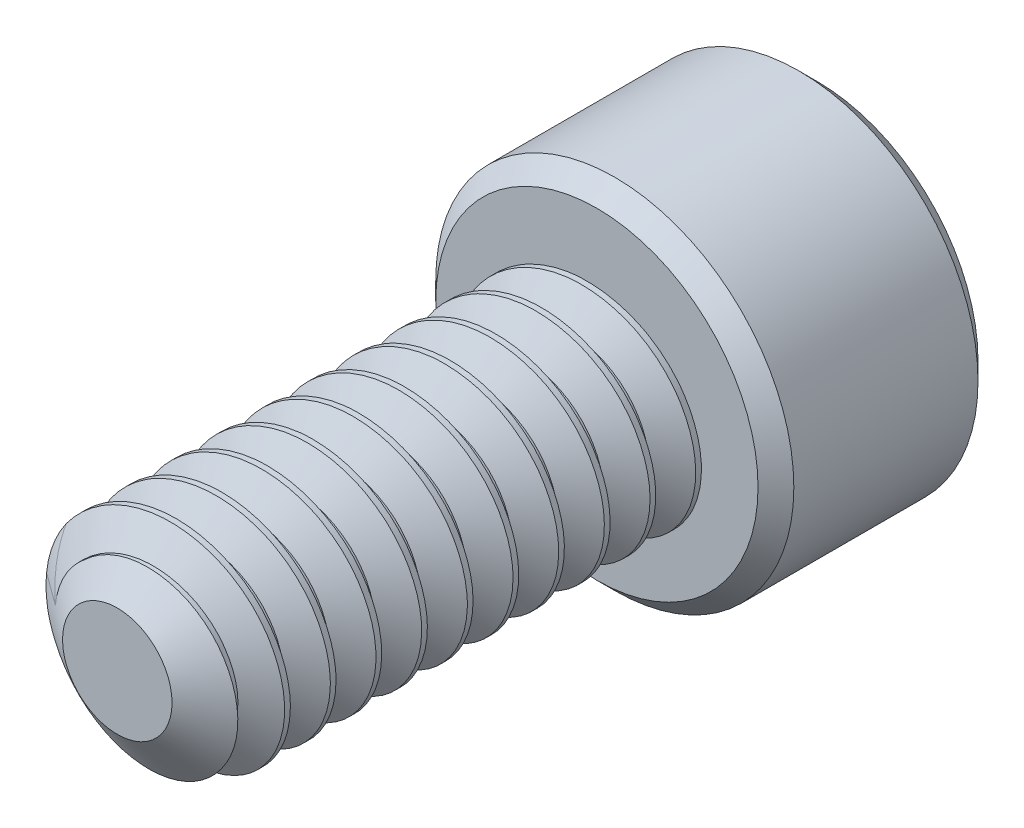
SolidWorks part; units mm, degrees
other "DetailItem1"
material "7075-T6 (SN)"
ref_plane "Front Plane" through (0, 0, 0) normal (0, 0, 1) x (1, 0, 0)
ref_plane "Top Plane" through (0, 0, 0) normal (0, 1, 0) x (1, 0, 0)
ref_plane "Right Plane" through (0, 0, 0) normal (1, 0, 0) x (0, 0, -1)
sketch "Sketch1" plane through (0, 0, 0) normal (0, 0, 1) x (1, 0, 0)
  circle A0 centre (0, 0) radius 1.0922
  dimension "OD" = 2.1844
extrude "Extrude1" add sketch "Sketch1" against normal blind 4.7625
sketch "Sketch2" plane through (0, 0, 0) normal (0, 0, 1) x (1, 0, 0)
  circle A0 centre (0, 0) radius 1.0922 construction
  circle A1 centre (0, 0) radius 1.0922
curve "Helix/Spiral1" pitch 0.4536 height 5.2161 radius 1.0922 centre (0, 0, 0) axis (0, 0, -1) start towards (0, 1, 0) parameters "pitch"=0.4536
sketch "Sketch3" plane through (0, 0, 0) normal (1, 0, 0) x (0, 0, -1)
  line L0 (-0.3969, 1.0922) -> (-0.2268, 0.7976)
  line L1 (-0.2268, 0.7976) -> (-0.1701, 0.7976)
  line L2 (-0.1701, 0.7976) -> (0, 1.0922)
  line L3 (-0.3969, 1.0922) -> (0, 1.0922)
  line L4 (-0.1984, 1.0922) -> (-0.1984, 0.7976) construction
  line L5 (-0.3118, 0.9449) -> (-0.085, 0.9449) construction
  line L6 (0, 1.0922) -> (0, -1.0922) construction
  dimension "D1" = 0.0567
  dimension "D2" = 0.2268
  dimension "D3" = 60
sweep "Cut-Sweep1" cut profiles "Sketch3" path "Helix/Spiral1" align with end faces yes
sketch "Sketch4" plane through (0, 0, 0) normal (1, 0, 0) x (0, 0, -1)
  line L0 (0.3841, 1.0922) -> (0, 0.5436)
  line L1 (0, 0.5436) -> (0, 1.0922)
  line L2 (0.3841, 1.0922) -> (0, 1.0922)
  line L3 (-0.3969, 1.0922) -> (0, 1.0922) construction
  line L4 (0, 0) -> (7.0209, 0) construction
  dimension "D1" = 55
  dimension "D2" = 0.254
revolve "Cut-Revolve1" cut sketch "Sketch4" angle 360 about L4
sketch "Sketch6" plane through (0, 0, -4.7625) normal (0, 0, -1) x (-1, 0, 0)
  circle A0 centre (0, 0) radius 1.778
  dimension "head dia" = 3.556
extrude "Extrude2" add sketch "Sketch6" along normal blind 2.1844
sketch "Sketch7" plane through (0, 0, -6.9469) normal (0, 0, -1) x (-1, 0, 0)
  line L1 (0, 1.1457) -> (-0.9922, 0.5728)
  line L2 (-0.9922, 0.5728) -> (-0.9922, -0.5728)
  line L3 (-0.9922, -0.5728) -> (0, -1.1457)
  line L4 (0, -1.1457) -> (0.9922, -0.5728)
  line L5 (0.9922, -0.5728) -> (0.9922, 0.5728)
  line L6 (0.9922, 0.5728) -> (0, 1.1457)
  circle A0 centre (0, 0) radius 0.9922 construction
  dimension "hex dia" = 1.9844
extrude "Cut-Extrude1" cut sketch "Sketch7" against normal blind 1.4883
sketch "Sketch8" plane through (0, 0, -6.9469) normal (0, 0, -1) x (-1, 0, 0)
  circle A0 centre (0, 0) radius 1.1457
extrude "Cut-Extrude2" cut sketch "Sketch8" against normal through all draft 45
chamfer "Chamfer1" distance 0.1778 angle 45 2 edges at (-1.778, 0, -6.9469) (-1.778, 0, -4.7625)
sketch "Sketch10" plane through (0, 0, -4.7625) normal (0, 0, 1) x (1, 0, 0)
  circle A1 centre (0, 0) radius 1.0922
  circle A2 centre (0, 0) radius 1.0922
  dimension "D1" = 0
ref_plane "Plane1" through (0, 0, 0) normal (0, 0, 1) x (1, 0, 0)
extrude "partial thread" [suppressed] add sketch "Sketch10" along normal up to surface (12.7 mm away) separate body up to plane "Plane1"
chamfer "Chamfer2" [suppressed] distance 0.0437 angle 45
combine bodies "Combine1" [suppressed] operation type add bodies to combine 107 108
sketch "Sketch9" plane through (0, 0, 0) normal (1, 0, 0) x (0, 0, -1)
  line L0 (0, 1.0922) -> (0, -1.0922) construction
  line L1 (1.1339, 1.0922) -> (1.1339, -1.0922) construction
  dimension "D1" = 1.1339
equation "\"D3@Helix/Spiral1\" = \"screw length@Extrude1\"+\"pitch@Helix/Spiral1\""
equation "\"D1@Sketch3\" = \"pitch@Helix/Spiral1\"*.125"
equation "\"D2@Sketch3\" = \"pitch@Helix/Spiral1\"*.5"
equation "\"D1@Cut-Extrude1\" = \"hex dia@Sketch7\"*.75"
equation "\"D1@Chamfer1\" = \"head dia@Sketch6\"*.05"
equation "\"D1@Sketch9\" = \"pitch@Helix/Spiral1\"*2.5"
equation "\"D1@Chamfer2\"=\"OD@Sketch1\"*.02"
